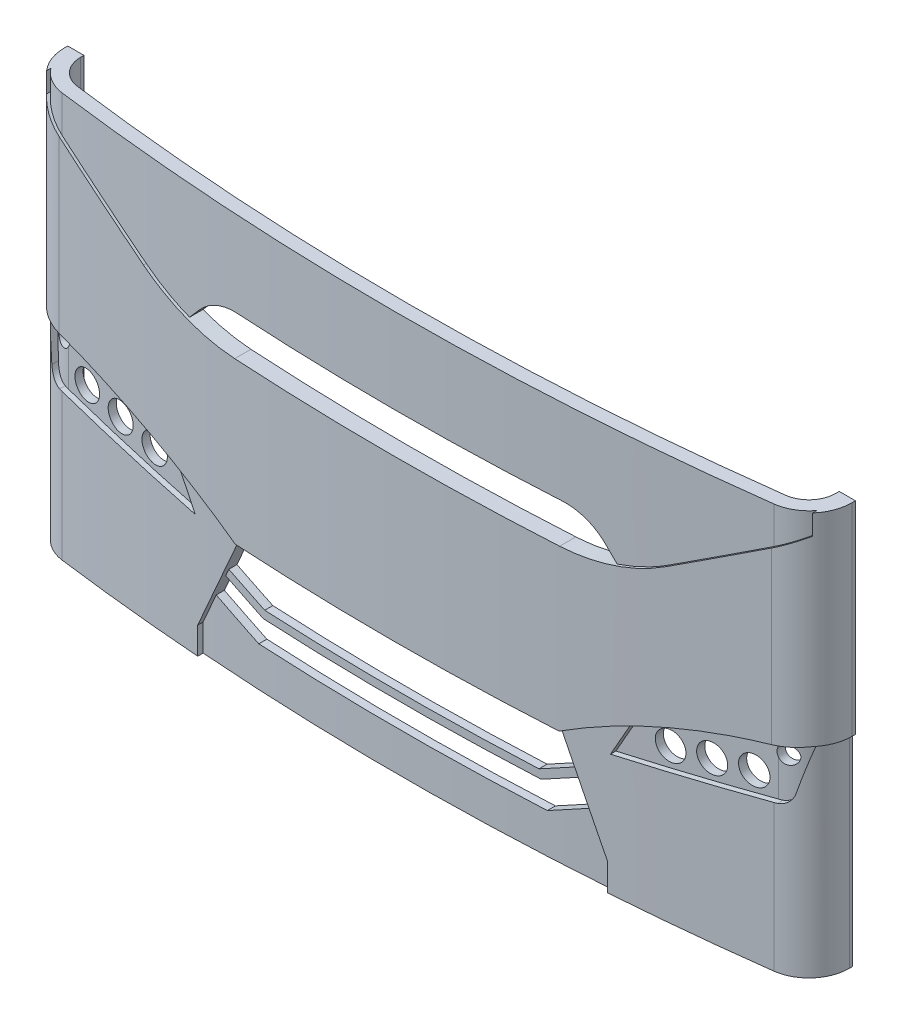
SolidWorks part; units mm, degrees
ref_plane "Front Plane" through (0, 0, 0) normal (0, 0, 1) x (1, 0, 0)
ref_plane "Top Plane" through (0, 0, 0) normal (0, 1, 0) x (1, 0, 0)
ref_plane "Right Plane" through (0, 0, 0) normal (1, 0, 0) x (0, 0, -1)
sketch "Sketch2" plane through (0, 0, 0) normal (0, 1, 0) x (1, 0, 0)
  line L0 (73, 5) -> (73, 4.3738)
  line L2 (-70, 5) -> (-70, 4.3738)
  line L4 (70, 5) -> (70, 4.3738)
  line L5 (-70, 5) -> (70, -5) construction
  line L6 (-70, -5) -> (70, 5) construction
  line L8 (-73, 5) -> (-73, 4.3738)
  line L9 (-70, 5) -> (-73, 5)
  line L10 (70, 5) -> (73, 5)
  line L11 (-73, 8) -> (73, 8) construction
  line L12 (-73, 8) -> (-73, 4.3738) construction
  line L13 (-70, 5) -> (70, 5) construction
  line L15 (73, 8) -> (73, 4.3738) construction
  arc A0 (-65.6436, -0.5846) -> (65.6436, -0.5846) centre (0, 505.124) ccw
  arc A1 (70, 4.3738) -> (65.6436, -0.5846) centre (65, 4.3738) cw
  arc A2 (-70, 4.3738) -> (-65.6436, -0.5846) centre (-65, 4.3738) ccw
  arc A3 (-73, 4.3738) -> (-66.0298, -3.5596) centre (-65, 4.3738) ccw
  arc A4 (-66.0298, -3.5596) -> (66.0298, -3.5596) centre (0, 505.124) ccw
  arc A5 (73, 4.3738) -> (66.0298, -3.5596) centre (65, 4.3738) cw
  point P0 (0, 0)
  dimension "D1" = 5
  dimension "D2" = 140
  dimension "D3" = 3
extrude "Boss-Extrude1" add sketch "Sketch2" along normal blind 75 contours A5 L0 L10 L4 A1 A0 A2 L2 L9 L8 A3 A4 region at (71.5344, 0, -4.6869)
ref_plane "Plane1" through (0, 0, 10) normal (0, 0, 1) x (1, 0, 0)
sketch "Sketch3" plane through (0, 0, 10) normal (0, 0, 1) x (1, 0, 0)
  line L0 (-73, 37.5) -> (73, 37.5) construction
  line L1 (-73, 75) -> (-73, 0) construction
  line L2 (73, 75) -> (73, 0) construction
  line L3 (0, 75) -> (0, 0) construction
  line L4 (66.0298, 75) -> (-66.0298, 75) construction
  line L5 (-66.0298, 0) -> (66.0298, 0) construction
  line L6 (-30, 22.5) -> (30, 22.5)
  line L8 (-73, 0) -> (-66.0298, 0) construction
  line L9 (-71, 0) -> (71, 0)
  line L10 (66.0298, 0) -> (73, 0) construction
  line L12 (-71, 37.5) -> (-73, 37.5)
  line L13 (-73, 37.5) -> (-73, 0)
  line L14 (-73, 0) -> (-71, 0)
  line L15 (71, 37.5) -> (73, 37.5)
  line L16 (73, 37.5) -> (73, 0)
  line L17 (73, 0) -> (71, 0)
  line L18 (-71, 75) -> (-71, 71.264)
  line L19 (-66.0298, 75) -> (-73, 75) construction
  line L20 (-71, 71.264) -> (-48.4264, 57.4026)
  line L21 (-30.1118, 52.2284) -> (30.1118, 52.2284)
  line L22 (48.4264, 57.4026) -> (71, 71.264)
  line L23 (71, 71.264) -> (71, 75)
  line L24 (73, 75) -> (66.0298, 75) construction
  line L25 (-66.0298, 75) -> (-71, 75)
  line L26 (66.0298, 75) -> (-66.0298, 75)
  line L27 (71, 75) -> (66.0298, 75)
  arc A0 (-71, 37.5) -> (-30, 22.5) centre (-86.9638, -69.6676) cw
  arc A1 (71, 37.5) -> (30, 22.5) centre (86.9638, -69.6676) ccw
  arc A2 (48.4264, 57.4026) -> (30.1118, 52.2284) centre (30.1118, 87.2284) cw
  arc A3 (-30.1118, 52.2284) -> (-48.4264, 57.4026) centre (-30.1118, 87.2284) cw
  point P41 (40, 52.2284)
  point P44 (-40, 52.2284)
  dimension "D10" = 35
  dimension "D1" = 37.5
  dimension "D2" = 60
  dimension "D3" = 15
  dimension "D4" = 2
  dimension "D5" = 30
  dimension "D6" = 2
  dimension "D7" = 2
  dimension "D8" = 80
  dimension "D9" = 40
extrude "Cut-Extrude1" cut sketch "Sketch3" against normal blind 75
sketch "Sketch8" plane through (0, 0, 0) normal (0, 1, 0) x (1, 0, 0)
  line L0 (-72.5, 4.3738) -> (-72.5, 5)
  line L1 (72.5, 4.3738) -> (72.5, 5)
  line L2 (-71, 5) -> (-73, 5) construction
  line L3 (-71, 5) -> (-72.5, 5)
  line L4 (71, 5) -> (73, 5) construction
  line L5 (71, 5) -> (72.5, 5)
  line L13 (71, 5) -> (70, 5) construction
  line L14 (71, 5) -> (70, 5)
  line L16 (-71, 5) -> (-70, 5) construction
  line L18 (-71, 5) -> (-70, 5)
  line L19 (70, 4.3738) -> (70, 5) construction
  line L20 (-70, 4.3738) -> (-70, 5) construction
  line L21 (70, 4.3738) -> (70, 5)
  line L22 (-70, 4.3738) -> (-70, 5)
  arc A0 (-72.5, 4.3738) -> (-65.9654, -3.0638) centre (-65, 4.3738) ccw
  arc A1 (-65.9654, -3.0638) -> (-48.6638, -5.0114) centre (0, 505.124) ccw
  arc A2 (-48.6638, -5.0114) -> (-30.2594, -6.4331) centre (0, 505.124) ccw
  arc A3 (-30.2594, -6.4331) -> (30.2594, -6.4331) centre (0, 505.124) ccw
  arc A4 (30.2594, -6.4331) -> (48.6638, -5.0114) centre (0, 505.124) ccw
  arc A5 (48.6638, -5.0114) -> (65.9654, -3.0638) centre (0, 505.124) ccw
  arc A6 (65.9654, -3.0638) -> (72.5, 4.3738) centre (65, 4.3738) ccw
  arc A31 (65.6436, -0.5846) -> (70, 4.3738) centre (65, 4.3738) ccw construction
  arc A32 (48.4264, -2.5227) -> (65.6436, -0.5846) centre (0, 505.124) ccw construction
  arc A37 (30.1118, -3.9374) -> (48.4264, -2.5227) centre (0, 505.124) ccw construction
  arc A38 (-30.1118, -3.9374) -> (30.1118, -3.9374) centre (0, 505.124) ccw construction
  arc A39 (-48.4264, -2.5227) -> (-30.1118, -3.9374) centre (0, 505.124) ccw construction
  arc A40 (-65.6436, -0.5846) -> (-48.4264, -2.5227) centre (0, 505.124) ccw construction
  arc A41 (-70, 4.3738) -> (-65.6436, -0.5846) centre (-65, 4.3738) ccw construction
  arc A42 (65.6436, -0.5846) -> (70, 4.3738) centre (65, 4.3738) ccw
  arc A43 (48.4264, -2.5227) -> (65.6436, -0.5846) centre (0, 505.124) ccw
  arc A44 (30.1118, -3.9374) -> (48.4264, -2.5227) centre (0, 505.124) ccw
  arc A45 (-30.1118, -3.9374) -> (30.1118, -3.9374) centre (0, 505.124) ccw
  arc A46 (-48.4264, -2.5227) -> (-30.1118, -3.9374) centre (0, 505.124) ccw
  arc A47 (-65.6436, -0.5846) -> (-48.4264, -2.5227) centre (0, 505.124) ccw
  arc A48 (-70, 4.3738) -> (-65.6436, -0.5846) centre (-65, 4.3738) ccw
  dimension "D1" = 2.5
extrude "Boss-Extrude4" add sketch "Sketch8" along normal up to surface (75 mm away) up to face at (-72.1208, 75, -3.3184)
sketch "Sketch9" plane through (0, 0, 10) normal (0, 0, 1) x (1, 0, 0)
  line L0 (-71, 37.5) -> (-68.9576, 29.4028)
  line L1 (-66.5419, 27.1774) -> (-38.4776, 22.5)
  line L2 (-38.4776, 22.5) -> (-42, 28.9123)
  line L3 (0, 75) -> (0, 0) construction
  line L4 (65.9654, 75) -> (-65.9654, 75) construction
  line L5 (38.4776, 22.5) -> (42, 28.9123)
  line L6 (66.5419, 27.1774) -> (38.4776, 22.5)
  line L7 (71, 37.5) -> (68.9576, 29.4028)
  arc A0 (-30, 22.5) -> (-65.9654, 36.6282) centre (-86.9638, -69.6676) ccw construction
  arc A1 (-65.9654, 36.6282) -> (-71, 37.5) centre (-86.9638, -69.6676) ccw construction
  arc A2 (-42, 28.9123) -> (-65.9654, 36.6282) centre (-86.9638, -69.6676) ccw
  arc A3 (-65.9654, 36.6282) -> (-71, 37.5) centre (-86.9638, -69.6676) ccw
  arc A4 (65.9654, 36.6282) -> (71, 37.5) centre (86.9638, -69.6676) cw
  arc A5 (42, 28.9123) -> (65.9654, 36.6282) centre (86.9638, -69.6676) cw
  arc A6 (68.9576, 29.4028) -> (66.5419, 27.1774) centre (66.0487, 30.1366) cw
  arc A7 (-66.5419, 27.1774) -> (-68.9576, 29.4028) centre (-66.0487, 30.1366) cw
  point P21 (68.4776, 27.5)
  point P24 (-68.4776, 27.5)
  dimension "D6" = 3
  dimension "D1" = 29
  dimension "D2" = 10
  dimension "D3" = 15
  dimension "D4" = 30
  dimension "D5" = 2.5224
extrude "Cut-Extrude3" cut sketch "Sketch9" against normal up to surface (15 mm away) up to face at (71.8333, 37.5, -5)
sketch "Sketch10" plane through (0, 0, 10) normal (0, 0, 1) x (1, 0, 0)
  line L0 (-38, 0) -> (-38, 5)
  line L1 (-65.9654, 0) -> (65.9654, 0) construction
  line L2 (-38, 5) -> (-30, 22.5)
  line L3 (-30, 22.5) -> (30, 22.5)
  line L4 (30, 22.5) -> (38, 5)
  line L5 (38, 5) -> (38, 0)
  line L6 (-38, 0) -> (38, 0)
  dimension "D1" = 8
  dimension "D2" = 8
  dimension "D3" = 5
  dimension "D4" = 5
extrude "Cut-Extrude4" cut sketch "Sketch10" against normal up to surface (15 mm away) up to face at (-71.3333, 37.0426, -5)
sketch "Sketch12" plane through (0, 75, 0) normal (0, 1, 0) x (1, 0, 0)
  line L0 (70, 5) -> (70, 4.3738) construction
  line L1 (-70, 4.3738) -> (-70, 5) construction
  line L2 (70, 5) -> (70, 4.3738)
  line L3 (-70, 4.3738) -> (-70, 5)
  line L4 (71.5, 5) -> (71.5, 4.3738)
  line L5 (-71.5, 4.3738) -> (-71.5, 5)
  line L6 (70, 5) -> (73, 5) construction
  line L7 (70, 5) -> (71.5, 5)
  line L8 (-70, 5) -> (-73, 5) construction
  line L9 (-70, 5) -> (-71.5, 5)
  arc A0 (-65.6436, -0.5846) -> (65.6436, -0.5846) centre (0, 505.124) ccw construction
  arc A1 (-65.6436, -0.5846) -> (65.6436, -0.5846) centre (0, 505.124) ccw
  arc A2 (65.6436, -0.5846) -> (70, 4.3738) centre (65, 4.3738) ccw construction
  arc A3 (-70, 4.3738) -> (-65.6436, -0.5846) centre (-65, 4.3738) ccw construction
  arc A4 (65.6436, -0.5846) -> (70, 4.3738) centre (65, 4.3738) ccw
  arc A5 (-70, 4.3738) -> (-65.6436, -0.5846) centre (-65, 4.3738) ccw
  arc A6 (65.8367, -2.0721) -> (71.5, 4.3738) centre (65, 4.3738) ccw
  arc A7 (-65.8367, -2.0721) -> (65.8367, -2.0721) centre (0, 505.124) ccw
  arc A8 (-71.5, 4.3738) -> (-65.8367, -2.0721) centre (-65, 4.3738) ccw
  dimension "D1" = 1.5
extrude "Boss-Extrude5" add sketch "Sketch12" against normal up to surface (75 mm away) up to face at (-61.873, 0, -0.4176)
sketch "Sketch13" plane through (0, 0, 10) normal (0, 0, 1) x (1, 0, 0)
  line L0 (-35.3747, 10.7428) -> (-26.9796, 7.355)
  line L1 (-38, 5) -> (-30, 22.5) construction
  line L2 (-26.9796, 7.355) -> (26.5259, 7.355)
  line L3 (26.5259, 7.355) -> (34.9259, 11.7246)
  line L4 (30, 22.5) -> (38, 5) construction
  line L5 (0, 22.5) -> (0, 0) construction
  line L6 (-30, 22.5) -> (30, 22.5) construction
  line L7 (-35.9361, 9.3518) -> (-27.2709, 5.855)
  line L8 (-27.2709, 5.855) -> (26.8927, 5.855)
  line L9 (26.8927, 5.855) -> (35.6181, 10.3939)
  line L12 (30, 22.5) -> (32.4346, 17.1744)
  line L13 (-35.3747, 10.7428) -> (-33.5019, 14.8396)
  line L14 (-30, 22.5) -> (30, 22.5)
  line L15 (-32.8776, 16.2052) -> (-25.8147, 13.355)
  line L16 (-25.8147, 13.355) -> (25.0586, 13.355)
  line L17 (25.0586, 13.355) -> (32.157, 17.0475)
  line L18 (-33.5019, 14.8396) -> (-26.1059, 11.855)
  line L19 (-26.1059, 11.855) -> (25.4255, 11.855)
  line L20 (25.4255, 11.855) -> (32.8492, 15.7168)
  line L21 (32.157, 17.0475) -> (32.4346, 17.1744)
  line L22 (32.8492, 15.7168) -> (33.0574, 15.812)
  line L23 (-32.8776, 16.2052) -> (-30, 22.5)
  line L24 (-33.6908, 14.9158) -> (-26.1059, 11.855) construction
  line L25 (-33.1294, 16.3068) -> (-25.8147, 13.355) construction
  line L26 (33.0574, 15.812) -> (34.9259, 11.7246)
  line L27 (30.1118, 52.2284) -> (-30.1118, 52.2284) construction
  line L28 (30.1118, 52.2284) -> (-30.1118, 52.2284)
  line L29 (-39.6275, 53.5468) -> (-37.2724, 55.2809)
  line L30 (-31.3431, 57.2284) -> (31.3431, 57.2284)
  line L31 (37.2724, 55.2809) -> (39.6275, 53.5468)
  arc A0 (-48.4264, 57.4026) -> (-30.1118, 52.2284) centre (-30.1118, 87.2284) ccw construction
  arc A1 (-39.6275, 53.5468) -> (-30.1118, 52.2284) centre (-30.1118, 87.2284) ccw
  arc A2 (30.1118, 52.2284) -> (48.4264, 57.4026) centre (30.1118, 87.2284) ccw construction
  arc A3 (30.1118, 52.2284) -> (39.6275, 53.5468) centre (30.1118, 87.2284) ccw
  arc A4 (31.3431, 57.2284) -> (37.2724, 55.2809) centre (31.3431, 47.2284) cw
  arc A5 (-31.3431, 57.2284) -> (-37.2724, 55.2809) centre (-31.3431, 47.2284) ccw
  point P39 (34.6275, 57.2284)
  point P42 (-34.6275, 57.2284)
  dimension "D8" = 10
  dimension "D1" = 1.5
  dimension "D2" = 8.3951
  dimension "D3" = 8.4
  dimension "D6" = 5
  dimension "D7" = 5
  dimension "D9" = 5
  dimension "D4" = 6
  dimension "D5" = 1.5
extrude "Cut-Extrude5" cut sketch "Sketch13" against normal up to surface (15 mm away) contours L23 L15 L16 L17 L21 L12 L14 | L26 L22 L20 L19 L18 L13 L0 L2 L3 region at (-0.0524, 10.0468, 10) region at (-0.2961, 18.0038, 10) up to face at (-71.8333, 37.5, -5)
sketch "Sketch14" plane through (0, 0, 10) normal (0, 0, 1) x (1, 0, 0)
  line L0 (30.1118, 52.2284) -> (-30.1118, 52.2284) construction
  line L1 (30.1118, 52.2284) -> (-30.1118, 52.2284)
  line L2 (-39.6275, 53.5468) -> (-37.614, 55.8348)
  line L3 (-30.107, 59.2284) -> (30.107, 59.2284)
  line L4 (37.614, 55.8348) -> (39.6275, 53.5468)
  arc A0 (30.1118, 52.2284) -> (48.4264, 57.4026) centre (30.1118, 87.2284) ccw construction
  arc A1 (-48.4264, 57.4026) -> (-30.1118, 52.2284) centre (-30.1118, 87.2284) ccw construction
  arc A2 (30.1118, 52.2284) -> (39.6275, 53.5468) centre (30.1118, 87.2284) ccw
  arc A3 (-39.6275, 53.5468) -> (-30.1118, 52.2284) centre (-30.1118, 87.2284) ccw
  arc A4 (37.614, 55.8348) -> (30.107, 59.2284) centre (30.107, 49.2284) ccw
  arc A5 (-30.107, 59.2284) -> (-37.614, 55.8348) centre (-30.107, 49.2284) ccw
  point P12 (34.6275, 59.2284)
  point P15 (-34.6275, 59.2284)
  dimension "D4" = 10
  dimension "D1" = 5
  dimension "D2" = 5
  dimension "D3" = 7
extrude "Cut-Extrude6" cut sketch "Sketch14" against normal up to surface (15 mm away) up to face at (-71.8333, 37.5, -5)
sketch "Sketch15" plane through (0, 0, 10) normal (0, 0, 1) x (1, 0, 0)
  line L0 (-38.4776, 22.5) -> (-65.9654, 27.0813) construction
  line L1 (-38.4776, 22.5) -> (-65.8367, 27.0599) construction
  line L2 (0, 75) -> (0, 0) construction
  line L3 (65.9654, 75) -> (-65.9654, 75) construction
  circle A0 centre (-61.8185, 29.9384) radius 2.6
  circle A1 centre (-54.8185, 28.7718) radius 2.6
  circle A2 centre (-47.8185, 27.6051) radius 2.6
  circle A3 centre (-67.1796, 34.6647) radius 1.6147
  circle A4 centre (47.8185, 27.6051) radius 2.6
  circle A5 centre (54.8185, 28.7718) radius 2.6
  circle A6 centre (61.8185, 29.9384) radius 2.6
  circle A7 centre (67.1796, 34.6647) radius 1.6147
  dimension "D1" = 5.2
  dimension "D2" = 5.2
  dimension "D3" = 5.2
  dimension "D9" = 3.2293
  dimension "D4" = 7
  dimension "D5" = 7
  dimension "D6" = 3.5
  dimension "D7" = 3.5
  dimension "D8" = 3.5
extrude "Cut-Extrude7" cut sketch "Sketch15" against normal up to surface (15 mm away) up to face at (-71.8333, 37.5, -5)
